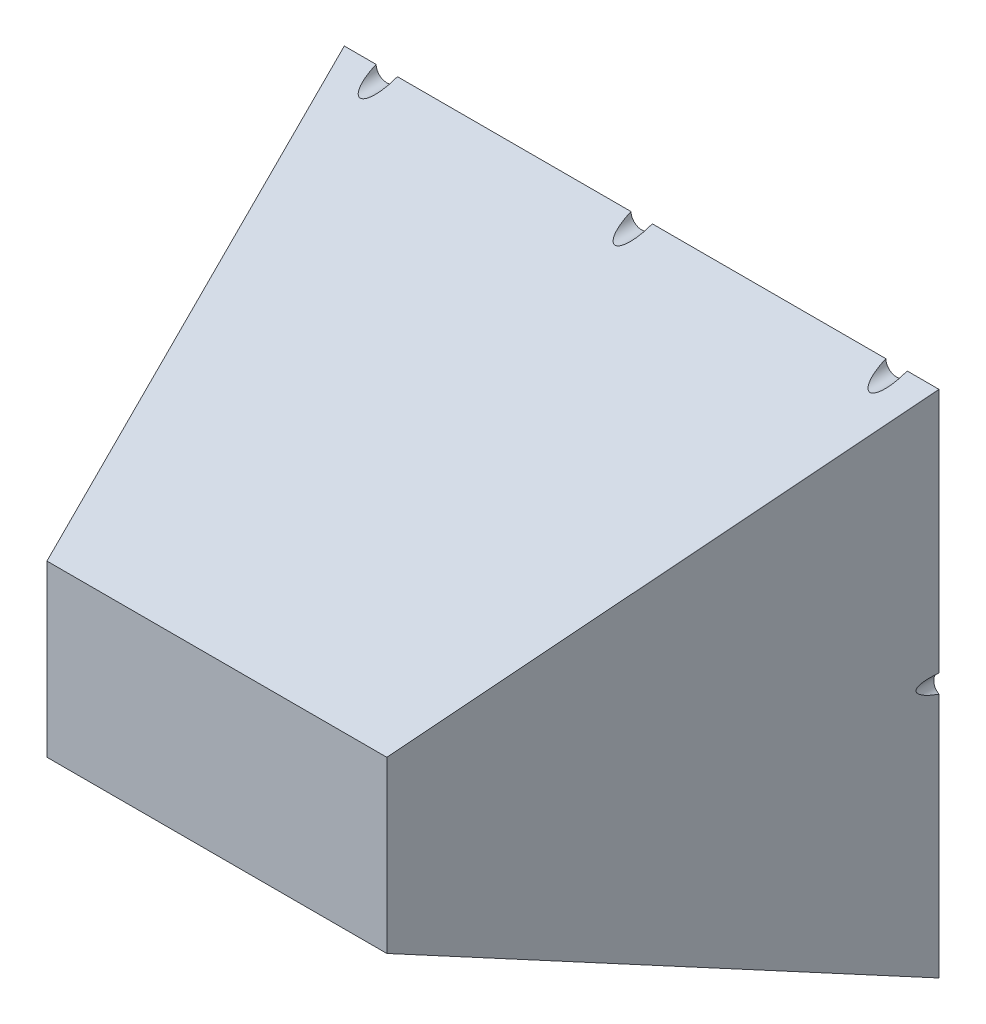
SolidWorks part; units mm, degrees
ref_plane "Front Plane" through (0, 0, 0) normal (0, 0, 1) x (1, 0, 0)
ref_plane "Top Plane" through (0, 0, 0) normal (0, 1, 0) x (1, 0, 0)
ref_plane "Right Plane" through (0, 0, 0) normal (1, 0, 0) x (0, 0, -1)
sketch "Sketch1" plane through (0, 0, 0) normal (0, 0, 1) x (1, 0, 0)
  line L1 (-177.8, -152.4) -> (177.8, -152.4)
  line L2 (-177.8, -152.4) -> (-177.8, 152.4)
  line L3 (-177.8, 152.4) -> (177.8, 152.4)
  line L4 (177.8, -152.4) -> (177.8, 152.4)
  line L5 (-177.8, -152.4) -> (177.8, 152.4) construction
  line L6 (-177.8, 152.4) -> (177.8, -152.4) construction
  point P0 (0, 0)
  dimension "D1" = 304.8
  dimension "D2" = 355.6
sketch "Sketch2" plane through (0, 0, 0) normal (0, 0, 1) x (1, 0, 0)
  line L0 (-193.675, 0) -> (-180.975, 0) construction
  line L1 (-193.675, -165.1) -> (193.675, -165.1) construction
  line L2 (-193.675, -165.1) -> (-193.675, 165.1) construction
  line L3 (-193.675, 165.1) -> (193.675, 165.1) construction
  line L4 (193.675, -165.1) -> (193.675, 165.1) construction
  line L5 (-193.675, -165.1) -> (193.675, 165.1) construction
  line L6 (-193.675, 165.1) -> (193.675, -165.1) construction
  line L7 (0, 165.1) -> (0, 152.4) construction
  line L8 (0, -181.61) -> (0, 181.61) construction
  line L9 (213.0425, 0) -> (-213.0425, 0) construction
  circle A0 centre (-180.975, 0) radius 6.35
  circle A1 centre (0, 152.4) radius 6.35
  circle A2 centre (152.4, 152.4) radius 6.35
  circle A3 centre (-152.4, 152.4) radius 6.35
  circle A4 centre (180.975, 0) radius 6.35
  circle A5 centre (152.4, -152.4) radius 6.35
  circle A6 centre (0, -152.4) radius 6.35
  circle A7 centre (-152.4, -152.4) radius 6.35
  point P0 (0, 0)
  dimension "D4" = 12.7
  dimension "D6" = 12.7
  dimension "D1" = 330.2
  dimension "D2" = 387.35
  dimension "D3" = 12.7
  dimension "D5" = 12.7
  dimension "D7" = 2
  dimension "D8" = 2
extrude "Boss-Extrude1" add sketch "Sketch1" along normal blind 254
chamfer "Chamfer1" distance 254 distance2 101.6 2 edges at (0, -152.4, 254) (0, 152.4, 254) first distance on face at (0, -152.4, 127) first distance on face at (0, 152.4, 127)
chamfer "Chamfer2" distance 254 distance2 76.2 2 edges at (177.8, 0, 254) (-177.8, 0, 254) first distance on face at (177.8, 0, 127) first distance on face at (-177.8, 0, 127)
extrude "Cut-Extrude1" cut sketch "Sketch2" along normal through all
